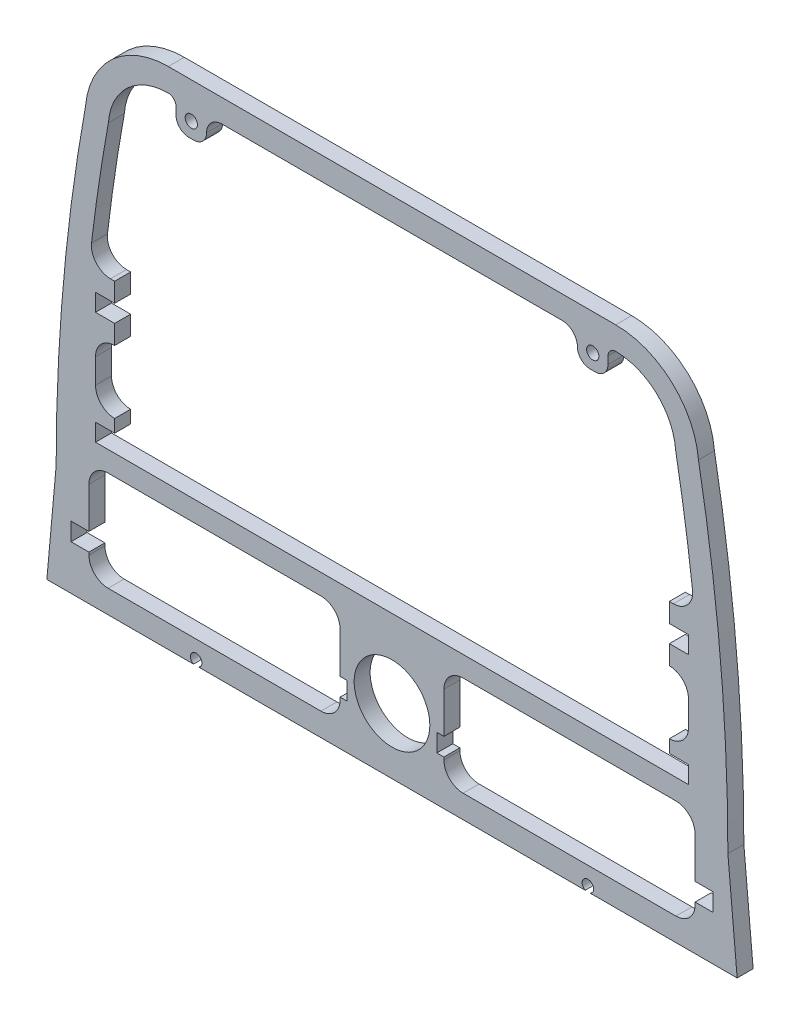
SolidWorks part; units mm, degrees
material "Delrin 2700 NC010, Low Viscosity Acetal Copolymer (SS)"
ref_plane "Front Plane" through (0, 0, 0) normal (0, 0, 1) x (1, 0, 0)
ref_plane "Top Plane" through (0, 0, 0) normal (0, 1, 0) x (1, 0, 0)
ref_plane "Right Plane" through (0, 0, 0) normal (1, 0, 0) x (0, 0, -1)
sketch "Sketch1" plane through (0, 0, 0) normal (0, 0, 1) x (1, 0, 0)
  line L0 (33.3676, -11.9888) -> (34.29, -22.225)
  line L1 (22.225, 27.94) -> (-22.225, 27.94)
  line L2 (-34.29, -22.225) -> (-30.4467, 20.4259) construction
  line L3 (-33.3676, -11.9888) -> (-33.3676, 14.6458) construction
  line L4 (-33.3676, -11.9888) -> (-34.29, -22.225)
  line L5 (16.9079, 25.654) -> (-16.9079, 25.654)
  line L6 (5.1562, -17.78) -> (5.1562, -19.939)
  line L7 (-30.1101, -19.939) -> (-5.1562, -19.939)
  line L8 (-34.29, -22.225) -> (34.29, -22.225)
  line L9 (-30.1101, -10.033) -> (-30.1101, -16.002)
  line L10 (18.4213, 24.1407) -> (18.4213, 24.1363)
  line L11 (19.6913, 22.8663) -> (20.1867, 22.8663)
  line L12 (21.4567, 24.1363) -> (21.4567, 24.8713)
  line L13 (-21.4567, 24.1363) -> (-21.4567, 24.8713)
  line L14 (-19.6913, 22.8663) -> (-20.1867, 22.8663)
  line L15 (-18.4213, 24.1407) -> (-18.4213, 24.1363)
  line L16 (29.4572, -8.001) -> (-29.4572, -8.001)
  line L17 (30.1101, -10.033) -> (5.1562, -10.033)
  line L18 (0, 18.415) -> (0, -18.415) construction
  line L19 (-1007.9925, 0) -> (48992.0075, 0) construction
  line L20 (-5.1562, -10.033) -> (-30.1101, -10.033)
  line L21 (19.939, 24.384) -> (21.4567, 24.384) construction
  line L22 (5.1562, -19.939) -> (30.1101, -19.939)
  line L23 (-5.1562, -10.033) -> (-5.1562, -16.002)
  line L24 (5.9491, -2.2098) -> (59.5431, -2.2098) construction
  line L25 (5.9491, -2.2098) -> (5.9491, -11.9888) construction
  line L26 (3.4091, -11.9888) -> (-3.4091, -11.9888) construction
  line L27 (59.5431, -2.2098) -> (59.5431, -11.9888) construction
  line L28 (-31.7887, -19.939) -> (31.7887, -19.939) construction
  line L29 (22.225, 25.654) -> (-22.225, 25.654) construction
  line L30 (-5.1562, -19.939) -> (-5.2268, -19.9899)
  line L31 (29.4572, -6.2738) -> (27.5522, -6.2738)
  line L32 (27.5522, -6.2738) -> (27.5522, -5.0038)
  line L33 (-30.1101, -16.002) -> (-31.8881, -16.002)
  line L34 (27.5522, -5.0038) -> (29.4572, -5.0038)
  line L35 (29.4572, 1.27) -> (27.5522, 1.27)
  line L36 (27.5522, 1.27) -> (27.5522, 3.175)
  line L37 (27.5522, 3.175) -> (29.4572, 3.175)
  line L38 (29.4572, 4.9022) -> (27.5522, 4.9022)
  line L39 (19.939, 24.384) -> (18.4213, 24.384) construction
  line L40 (27.5522, 4.9022) -> (27.5522, 6.8072)
  line L41 (27.5522, 6.8072) -> (30.0922, 6.8072)
  line L42 (19.939, 24.384) -> (19.939, 22.8663) construction
  line L43 (5.1562, -10.033) -> (5.1562, -16.002)
  line L44 (-29.4572, -6.2738) -> (-29.4572, -8.001)
  line L45 (-29.4572, -6.2738) -> (-27.5522, -6.2738)
  line L46 (-27.5522, -6.2738) -> (-27.5522, -5.0038)
  line L47 (-27.5522, -5.0038) -> (-29.4572, -5.0038)
  line L48 (-29.4572, 1.27) -> (-29.4572, -5.0038)
  line L49 (-29.4572, 1.27) -> (-27.5522, 1.27)
  line L50 (-27.5522, 1.27) -> (-27.5522, 3.175)
  line L51 (-27.5522, 3.175) -> (-29.4572, 3.175)
  line L52 (-29.4572, 4.9022) -> (-29.4572, 3.175)
  line L53 (-31.8881, -16.002) -> (-31.8881, -17.78)
  line L54 (-31.8881, -17.78) -> (-30.1101, -17.78)
  line L55 (-5.1562, -16.002) -> (-4.4561, -16.002)
  line L56 (-4.4561, -16.002) -> (-4.4561, -17.78)
  line L57 (-4.4561, -17.78) -> (-5.1562, -17.78)
  line L58 (-30.1101, -10.033) -> (-30.1101, -19.939) construction
  line L59 (-30.1101, -14.986) -> (-33.8821, -14.986) construction
  line L60 (-30.1101, -14.986) -> (-0.9396, -14.986) construction
  line L61 (-5.1562, -17.78) -> (-5.1562, -19.939)
  line L62 (-30.1101, -19.939) -> (-30.1101, -17.78)
  line L63 (30.1101, -19.939) -> (30.1101, -17.78)
  line L64 (-31.0816, -12.0913) -> (-31.7887, -19.939) construction
  line L65 (30.1101, -10.033) -> (30.1101, -16.002)
  line L66 (31.8881, -17.78) -> (30.1101, -17.78)
  line L67 (31.8881, -16.002) -> (31.8881, -17.78)
  line L68 (30.1101, -16.002) -> (31.8881, -16.002)
  line L69 (5.1562, -16.002) -> (4.4561, -16.002)
  line L70 (4.4561, -16.002) -> (4.4561, -17.78)
  line L71 (4.4561, -17.78) -> (5.1562, -17.78)
  line L72 (29.4572, 4.9022) -> (29.4572, 3.175)
  line L73 (31.0816, -12.0913) -> (31.7887, -19.939) construction
  line L74 (29.4572, 1.27) -> (29.4572, -5.0038)
  line L75 (29.4572, -6.2738) -> (29.4572, -8.001)
  line L76 (-29.4572, 4.9022) -> (-27.5522, 4.9022)
  line L77 (-27.5522, 4.9022) -> (-27.5522, 6.8072)
  line L78 (-27.5522, 6.8072) -> (-30.0922, 6.8072)
  arc A0 (22.225, 27.94) -> (30.4467, 20.4259) centre (22.225, 19.685) cw
  arc A1 (-22.225, 27.94) -> (-30.4467, 20.4259) centre (-22.225, 19.685) ccw
  arc A2 (33.3676, -11.9888) -> (30.4467, 20.4259) centre (-147.9525, -11.9888) ccw
  circle A3 centre (0, -15.748) radius 3.7592
  circle A4 centre (19.4575, -21.717) radius 0.5715
  arc A5 (-33.3676, -11.9888) -> (-30.4467, 20.4259) centre (147.9525, -11.9888) cw
  arc A8 (20.1867, 22.8663) -> (21.4567, 24.1363) centre (20.1867, 24.1363) ccw
  circle A9 centre (-19.939, 24.384) radius 0.6096
  circle A10 centre (19.939, 24.384) radius 0.6096
  arc A11 (18.4213, 24.1363) -> (19.6913, 22.8663) centre (19.6913, 24.1363) ccw
  circle A12 centre (-19.4575, -21.717) radius 0.5715
  arc A13 (18.4213, 24.1407) -> (16.9079, 25.654) centre (16.9079, 24.1407) ccw
  arc A14 (22.2416, 25.654) -> (21.4567, 24.8713) centre (22.2394, 24.8713) ccw
  arc A15 (-22.2416, 25.654) -> (-21.4567, 24.8713) centre (-22.2394, 24.8713) cw
  arc A16 (-20.1867, 22.8663) -> (-21.4567, 24.1363) centre (-20.1867, 24.1363) cw
  arc A17 (-18.4213, 24.1363) -> (-19.6913, 22.8663) centre (-19.6913, 24.1363) cw
  arc A18 (-22.2416, 25.654) -> (-28.1777, 20.1262) centre (-22.225, 19.685) ccw
  arc A19 (-18.4213, 24.1407) -> (-16.9079, 25.654) centre (-16.9079, 24.1407) cw
  arc A20 (31.0816, -12.0913) -> (31.0816, -11.9888) centre (-147.9525, -11.9888) ccw
  arc A23 (22.2416, 25.654) -> (28.1777, 20.1262) centre (22.225, 19.685) cw
  arc A25 (-22.225, 25.654) -> (-28.1777, 20.1262) centre (-22.225, 19.685) ccw construction
  arc A26 (22.225, 25.654) -> (28.1777, 20.1262) centre (22.225, 19.685) cw construction
  arc A28 (-31.0816, -12.0913) -> (-28.1777, 20.1262) centre (147.9525, -11.9888) cw construction
  arc A30 (31.0816, -12.0913) -> (28.1777, 20.1262) centre (-147.9525, -11.9888) ccw construction
  arc A31 (30.0922, 6.8072) -> (28.1777, 20.1262) centre (-147.9525, -11.9888) ccw
  arc A33 (-30.0922, 6.8072) -> (-28.1777, 20.1262) centre (147.9525, -11.9888) cw
  point P0 (0, 0)
  point P1 (0, 27.94)
  point P26 (0, -22.225)
  point P31 (0, -11.9888)
  point P121 (-31.359, -14.986)
  dimension "D4" = 2.286
  dimension "D6" = 8.255
  dimension "D7" = 19.4575
  dimension "D8" = 50.165
  dimension "D9" = 15.748
  dimension "D5" = 1.2192
  dimension "D17" = 1.143
  dimension "D3" = 7.5184
  dimension "D18" = 1.27
  dimension "D19" = 1.27
  dimension "D26" = 11.176
  dimension "D28" = 0.7827
  dimension "D29" = 1.5133
  dimension "D32" = 1.778
  dimension "D2" = 44.45
  dimension "D10" = 0.508
  dimension "D11" = 1.27
  dimension "D12" = 68.58
  dimension "D13" = 19.939
  dimension "D14" = 22.225
  dimension "D15" = 53.594
  dimension "D16" = 9.779
  dimension "D20" = 5.1562
  dimension "D21" = 11.938
  dimension "D22" = 2.032
  dimension "D23" = 1.7272
  dimension "D24" = 1.27
  dimension "D25" = 1.905
  dimension "D27" = 0.4954
  dimension "D30" = 1.905
  dimension "D31" = 1.7272
  dimension "D33" = 1.778
  dimension "D34" = 2.159
  dimension "D35" = 24.9539
  dimension "D36" = 27.432
  dimension "D37" = 1.905
  dimension "D38" = 2.54
extrude "Boss-Extrude1" add sketch "Sketch1" along normal blind 1.5875 contours L8 A12 A4 L0 A2 A0 L1 A1 A5 L4 L74 L16 A18 A15 L13 A16 L14 A17 L15 A19 L5 A13 L10 A11 L11 A8 L12 A14 A23 A20 L22 L43 L17 A10 A9 A3 L20 region at (32.9825, -17.1832, 0)
ref_axis "Axis1" through (0, -15.748, 0) along (0, 0, 1)
fillet "Fillet1" radius 1.905 8 edges at (-5.1562, -10.033, 0.7937) (5.1562, -10.033, 0.7937) (-5.1562, -19.939, 0.7937) (-30.1101, -19.939, 0.7937) (-30.1101, -10.033, 0.7937) (5.1562, -19.939, 0.7937) (30.1101, -19.939, 0.7937) (30.1101, -10.033, 0.7937)
fillet "Fillet2" radius 1.905 6 edges at (-29.4572, 1.27, 0.7937) (-29.4572, -5.0038, 0.7937) (-30.0922, 6.8072, 0.7937) (29.4572, -5.0038, 0.7937) (29.4572, 1.27, 0.7937) (30.0922, 6.8072, 0.7937)
